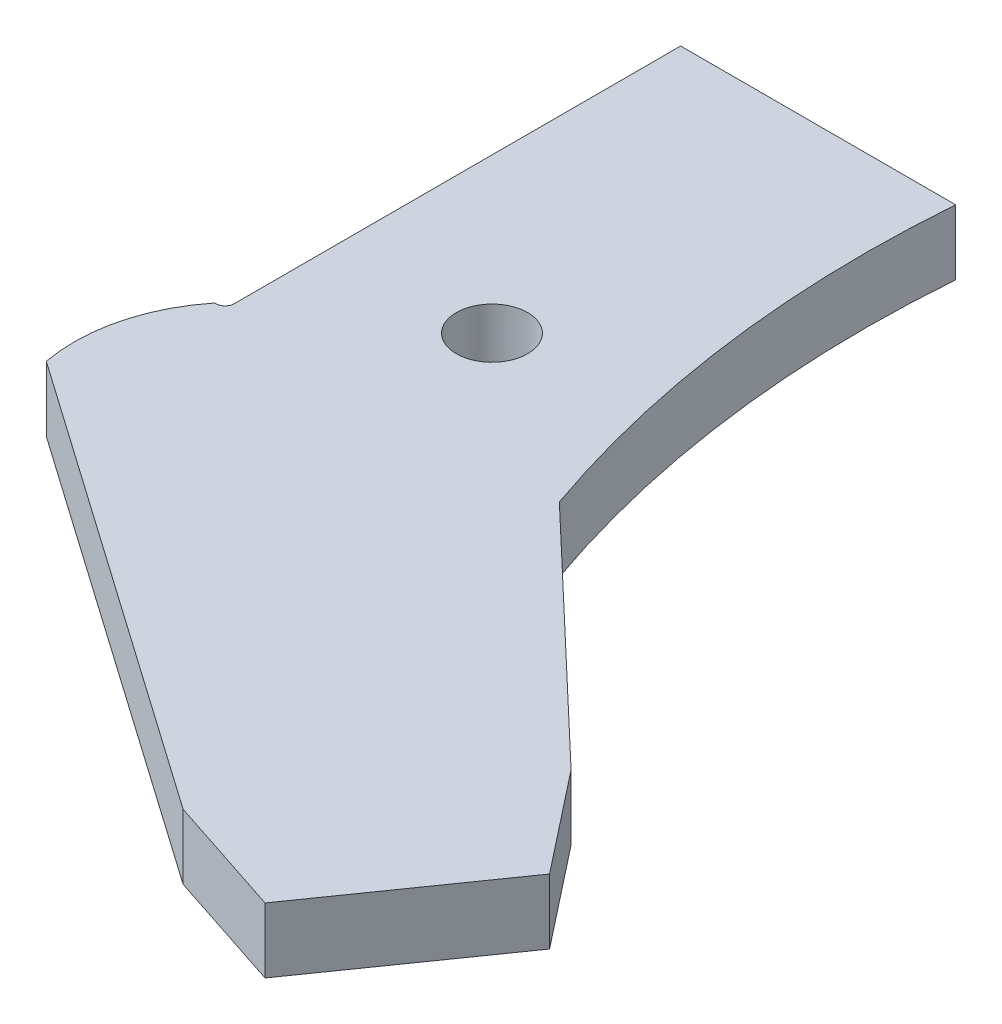
SolidWorks part; units mm, degrees
ref_plane "Front Plane" through (0, 0, 0) normal (0, 0, 1) x (1, 0, 0)
ref_plane "Top Plane" through (0, 0, 0) normal (0, 1, 0) x (1, 0, 0)
ref_plane "Right Plane" through (0, 0, 0) normal (1, 0, 0) x (0, 0, -1)
sketch "Sketch1" plane through (0, 0, 0) normal (0, 1, 0) x (1, 0, 0)
  line L0 (47.0297, 0) -> (-47.0297, 0)
  line L1 (-47.0297, -28.9719) -> (45.8391, -28.9719) construction
  line L2 (-47.0297, 0) -> (-47.0297, -152.5984)
  line L3 (-47.0297, -155.7734) -> (-50.6016, -155.7734) construction
  line L4 (-47.0297, -155.7734) -> (-47.0297, -201.8109) construction
  line L5 (-47.0297, -201.8109) -> (-62.1109, -201.8109) construction
  line L6 (-47.0297, -180.7766) -> (-62.1109, -180.7766) construction
  line L7 (-47.0297, -155.7734) -> (67.2703, -155.7734) construction
  line L8 (5.7547, -125.2141) -> (5.7547, -155.7734) construction
  line L9 (-50.6016, -155.7734) -> (-50.2047, -155.7734)
  line L10 (-62.1109, -201.8109) -> (93.9375, -311.0772)
  line L11 (93.9375, -311.0772) -> (135.6827, -324.8037)
  line L12 (135.6827, -324.8037) -> (175.747, -267.5859)
  line L13 (175.747, -267.5859) -> (148.5707, -233.053)
  line L14 (135.6827, -324.8037) -> (128.3982, -335.2069) construction
  line L15 (128.3982, -335.2069) -> (93.9375, -311.0772) construction
  line L16 (175.747, -267.5859) -> (183.0314, -257.1827) construction
  line L17 (148.5707, -233.053) -> (183.0314, -257.1827) construction
  line L18 (67.2703, -155.7734) -> (148.5707, -233.053)
  arc A0 (-62.1109, -201.8109) -> (-50.6016, -155.7734) centre (-6.35, -191.2937) cw
  circle A1 centre (5.7547, -117.2766) radius 7.9375
  arc A2 (47.0297, 0) -> (67.2703, -155.7734) centre (425.2702, -30.0545) ccw
  arc A3 (-47.0297, -152.5984) -> (-50.2047, -155.7734) centre (-50.2047, -152.5984) cw
  point P4 (0, 0)
  dimension "D11" = 15.875
  dimension "D14" = 3.175
  dimension "D1" = 94.0594
  dimension "D2" = 92.8688
  dimension "D3" = 28.9719
  dimension "D4" = 155.7734
  dimension "D5" = 25.0031
  dimension "D6" = 46.0375
  dimension "D7" = 15.0812
  dimension "D8" = 3.5719
  dimension "D9" = 15.0812
  dimension "D10" = 114.3
  dimension "D12" = 30.5594
  dimension "D13" = 52.7844
  dimension "D15" = 35
  dimension "D16" = 190.5
  dimension "D17" = 69.85
  dimension "D18" = 90
  dimension "D19" = 180
  dimension "D20" = 180
  dimension "D21" = 42.0687
  dimension "D22" = 12.7
  dimension "D23" = 42.0688
  dimension "D24" = 12.7
  dimension "D25" = 90
extrude "Boss-Extrude1" add sketch "Sketch1" along normal blind 22.225
sketch "Sketch2" plane through (0, 22.225, 0) normal (0, 1, 0) x (1, 0, 0)
  circle A0 centre (5.7547, -117.2766) radius 12.2039
  dimension "D1" = 24.4078
extrude "Cut-Extrude1" cut sketch "Sketch2" against normal up to surface (22.225 mm away) up to face at (36.2478, 0, 178.0641)
